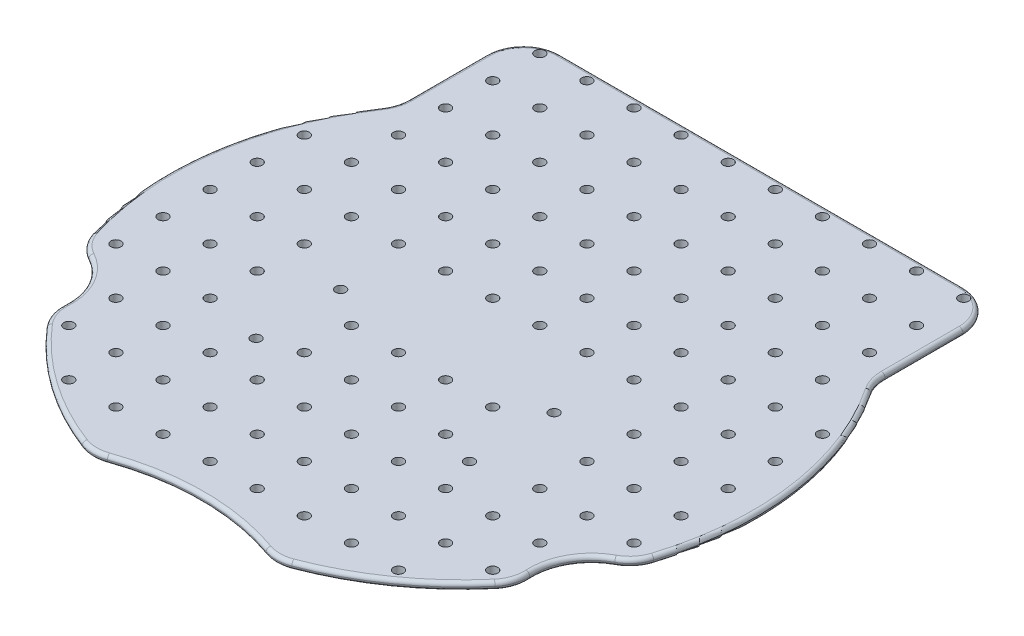
SolidWorks part; units mm, degrees
ref_plane "Front Plane" through (0, 0, 0) normal (0, 0, 1) x (1, 0, 0)
ref_plane "Top Plane" through (0, 0, 0) normal (0, 1, 0) x (1, 0, 0)
ref_plane "Right Plane" through (0, 0, 0) normal (1, 0, 0) x (0, 0, -1)
sketch "Sketch2" plane through (0, 0, 0) normal (0, 1, 0) x (1, 0, 0)
  line L0 (0, 0) -> (0, 108.8103) construction
  line L1 (0, 0) -> (176.5905, 0) construction
sketch "Top_lay" plane through (0, 0, 0) normal (0, 1, 0) x (1, 0, 0)
  line L0 (0, 0) -> (0, 108.8103) construction
  line L1 (-24.7551, -76.0736) -> (24.7551, -76.0736)
  arc A0 (24.7551, -76.0736) -> (-24.7551, -76.0736) centre (0, 0) ccw
  point P3 (0, -76.0223)
  dimension "D1" = 160
extrude "Boss-Extrude2" add sketch "Top_lay" along normal mid plane 2
sketch "Motor_Spacing" plane through (0, 1, 0) normal (0, 1, 0) x (1, 0, 0)
  line L0 (0, 0) -> (0, 108.8103) construction
  line L2 (64.7199, 81.3288) -> (-64.7199, 81.3288)
  line L3 (64.7199, 81.3288) -> (64.7199, 46.3288)
  line L4 (64.7199, 46.3288) -> (-64.7199, 46.3288)
  line L5 (-64.7199, 81.3288) -> (-64.7199, 46.3288)
  line L6 (64.7199, 81.3288) -> (-64.7199, 46.3288) construction
  line L7 (64.7199, 46.3288) -> (-64.7199, 81.3288) construction
  point P2 (0, 63.8288)
  dimension "D1" = 35
extrude "Boss-Extrude6" add sketch "Motor_Spacing" against normal blind 2
sketch "Clamps" plane through (0, 1, 0) normal (0, 1, 0) x (1, 0, 0)
  line L5 (0, 0) -> (0, 108.9952) construction
  line L11 (-64.7199, 81.3288) -> (-71.8617, 81.3288)
  line L12 (-64.7199, 81.3288) -> (-64.7199, 46.8057)
  line L13 (-64.7199, 46.8057) -> (-71.8617, 46.8057)
  line L14 (-71.8617, 81.3288) -> (-71.8617, 46.8057)
  line L15 (64.7199, 46.8057) -> (71.8617, 46.8057)
  line L16 (64.7199, 81.3288) -> (64.7199, 46.8057)
  line L17 (64.7199, 81.3288) -> (71.8617, 81.3288)
  line L18 (71.8617, 81.3288) -> (71.8617, 46.8057)
sketch "RPi_L298N_hatch" plane through (0, -1, 0) normal (0, -1, 0) x (1, 0, 0)
  line L0 (0, 0) -> (0, -108.8103) construction
  line L1 (-32.5, 0.5353) -> (32.5, 0.5353)
  line L2 (-32.5, 0.5353) -> (-32.5, 30.5353)
  line L3 (-32.5, 30.5353) -> (32.5, 30.5353)
  line L4 (32.5, 0.5353) -> (32.5, 30.5353)
  line L5 (-32.5, 0.5353) -> (32.5, 30.5353) construction
  line L6 (-32.5, 30.5353) -> (32.5, 0.5353) construction
  line L8 (-22, -11.6596) -> (22, -11.6596)
  line L9 (-22, -11.6596) -> (-22, -55.6596)
  line L10 (-22, -55.6596) -> (22, -55.6596)
  line L11 (22, -11.6596) -> (22, -55.6596)
  line L12 (-22, -11.6596) -> (22, -55.6596) construction
  line L13 (-22, -55.6596) -> (22, -11.6596) construction
  point P0 (0, 15.5353)
  point P7 (0, -33.6596)
  point P12 (0, -89.9264)
  dimension "D1" = 65
  dimension "D2" = 30
  dimension "D3" = 44
  dimension "D4" = 44
sketch "PIR_ULTRA" plane through (0, -1, 0) normal (0, -1, 0) x (1, 0, 0)
  line L0 (0, 0) -> (0, -108.8103) construction
  line L12 (22.5, 64.0502) -> (-22.5, 64.0502)
  line L13 (22.5, 64.0502) -> (22.5, 59.0502)
  line L18 (22.5, 59.0502) -> (-22.5, 59.0502)
  line L19 (-22.5, 64.0502) -> (-22.5, 59.0502)
  line L20 (22.5, 64.0502) -> (-22.5, 59.0502) construction
  line L21 (22.5, 59.0502) -> (-22.5, 64.0502) construction
  point P7 (0, 61.5502)
  dimension "D1" = 5
  dimension "D2" = 45
sketch "Sketch4" plane through (0, 1, 0) normal (0, 1, 0) x (1, 0, 0)
  line L0 (30.9083, 77.9119) -> (33.3167, 77.8645) construction
  line L5 (-70.5204, 79.9042) -> (-69.9756, 79.8935) construction
  line L6 (-70.5204, 77.1986) -> (-69.9756, 77.2093) construction
  line L7 (30.9083, 79.1909) -> (33.3167, 79.2382) construction
  line L8 (-31.8745, -49.4486) -> (-31.8745, -62.2486) construction
  line L9 (-58.2826, 77.4389) -> (-56.6233, 77.4715) construction
  line L10 (-58.2826, 79.6638) -> (-56.6233, 79.6312) construction
  line L11 (-45.7424, 79.4175) -> (-43.5734, 79.3749) construction
  line L12 (-45.7424, 77.6853) -> (-43.5734, 77.7279) construction
  line L13 (-33.1029, 77.9335) -> (-30.6228, 77.9823) construction
  line L14 (-33.1029, 79.1692) -> (-30.6228, 79.1205) construction
  line L15 (-20.3992, 78.9197) -> (-17.7363, 78.8674) construction
  line L16 (-20.3992, 78.1831) -> (-17.7363, 78.2354) construction
  line L17 (-7.6444, 78.6691) -> (-4.901, 78.6152) construction
  line L18 (-7.6444, 78.4336) -> (-4.901, 78.4875) construction
  line L19 (5.157, 78.6851) -> (7.8877, 78.7387) construction
  line L20 (5.157, 78.4177) -> (7.8877, 78.364) construction
  line L21 (18.0058, 78.1653) -> (20.629, 78.1138) construction
  line L22 (18.0058, 78.9375) -> (20.629, 78.989) construction
  line L23 (56.9741, 77.3998) -> (58.4311, 77.3712) construction
  line L24 (56.9741, 79.7029) -> (58.4311, 79.7315) construction
  line L25 (43.8811, 79.4457) -> (45.934, 79.4861) construction
  line L26 (43.8811, 77.657) -> (45.934, 77.6167) construction
  line L27 (-31.8745, -62.2486) -> (-31.8745, -55.8486) construction
  line L28 (-31.8745, -55.8486) -> (41.6099, -55.8486) construction
  circle A1 centre (-70.2745, 78.5514) radius 1.375
  circle A2 centre (-57.4745, 78.5514) radius 1.375
  circle A3 centre (-44.6745, 78.5514) radius 1.375
  circle A4 centre (-31.8745, 78.5514) radius 1.375
  circle A5 centre (-19.0745, 78.5514) radius 1.375
  circle A6 centre (-6.2745, 78.5514) radius 1.375
  circle A7 centre (6.5255, 78.5514) radius 1.375
  circle A8 centre (19.3255, 78.5514) radius 1.375
  circle A9 centre (32.1255, 78.5514) radius 1.375
  circle A10 centre (44.9255, 78.5514) radius 1.375
  circle A11 centre (57.7255, 78.5514) radius 1.375
  circle A12 centre (70.5255, 78.5514) radius 1.375
  circle A13 centre (-57.4745, 65.7514) radius 1.375
  circle A14 centre (-44.6745, 65.7514) radius 1.375
  circle A15 centre (-31.8745, 65.7514) radius 1.375
  circle A16 centre (-19.0745, 65.7514) radius 1.375
  circle A17 centre (-6.2745, 65.7514) radius 1.375
  circle A18 centre (6.5255, 65.7514) radius 1.375
  circle A19 centre (19.3255, 65.7514) radius 1.375
  circle A20 centre (32.1255, 65.7514) radius 1.375
  circle A21 centre (44.9255, 65.7514) radius 1.375
  circle A22 centre (57.7255, 65.7514) radius 1.375
  circle A23 centre (70.5255, 65.7514) radius 1.375
  circle A24 centre (-57.4745, 52.9514) radius 1.375
  circle A25 centre (-44.6745, 52.9514) radius 1.375
  circle A26 centre (-31.8745, 52.9514) radius 1.375
  circle A27 centre (-19.0745, 52.9514) radius 1.375
  circle A28 centre (-6.2745, 52.9514) radius 1.375
  circle A29 centre (6.5255, 52.9514) radius 1.375
  circle A30 centre (19.3255, 52.9514) radius 1.375
  circle A31 centre (32.1255, 52.9514) radius 1.375
  circle A32 centre (44.9255, 52.9514) radius 1.375
  circle A33 centre (57.7255, 52.9514) radius 1.375
  circle A34 centre (70.5255, 52.9514) radius 1.375
  circle A35 centre (-57.4745, 40.1514) radius 1.375
  circle A36 centre (-44.6745, 40.1514) radius 1.375
  circle A37 centre (-31.8745, 40.1514) radius 1.375
  circle A38 centre (-19.0745, 40.1514) radius 1.375
  circle A39 centre (-6.2745, 40.1514) radius 1.375
  circle A40 centre (6.5255, 40.1514) radius 1.375
  circle A41 centre (19.3255, 40.1514) radius 1.375
  circle A42 centre (32.1255, 40.1514) radius 1.375
  circle A43 centre (44.9255, 40.1514) radius 1.375
  circle A44 centre (57.7255, 40.1514) radius 1.375
  circle A46 centre (-57.4745, 27.3514) radius 1.375
  circle A47 centre (-44.6745, 27.3514) radius 1.375
  circle A48 centre (-31.8745, 27.3514) radius 1.375
  circle A49 centre (-19.0745, 27.3514) radius 1.375
  circle A50 centre (-6.2745, 27.3514) radius 1.375
  circle A51 centre (6.5255, 27.3514) radius 1.375
  circle A52 centre (19.3255, 27.3514) radius 1.375
  circle A53 centre (32.1255, 27.3514) radius 1.375
  circle A54 centre (44.9255, 27.3514) radius 1.375
  circle A55 centre (57.7255, 27.3514) radius 1.375
  circle A56 centre (70.5255, 27.3514) radius 1.375
  circle A57 centre (-57.4745, 14.5514) radius 1.375
  circle A58 centre (-44.6745, 14.5514) radius 1.375
  circle A59 centre (-31.8745, 14.5514) radius 1.375
  circle A60 centre (-19.0745, 14.5514) radius 1.375
  circle A61 centre (-6.2745, 14.5514) radius 1.375
  circle A62 centre (6.5255, 14.5514) radius 1.375
  circle A63 centre (19.3255, 14.5514) radius 1.375
  circle A64 centre (32.1255, 14.5514) radius 1.375
  circle A65 centre (44.9255, 14.5514) radius 1.375
  circle A66 centre (57.7255, 14.5514) radius 1.375
  circle A67 centre (70.5255, 14.5514) radius 1.375
  circle A68 centre (-57.4745, 1.7514) radius 1.375
  circle A69 centre (-44.6745, 1.7514) radius 1.375
  circle A76 centre (44.9255, 1.7514) radius 1.375
  circle A77 centre (57.7255, 1.7514) radius 1.375
  circle A78 centre (70.5255, 1.7514) radius 1.375
  circle A79 centre (-57.4745, -11.0486) radius 1.375
  circle A80 centre (-44.6745, -11.0486) radius 1.375
  circle A82 centre (-19.0745, -11.0486) radius 1.375
  circle A83 centre (-6.2745, -11.0486) radius 1.375
  circle A84 centre (6.5255, -11.0486) radius 1.375
  circle A85 centre (19.3255, -11.0486) radius 1.375
  circle A87 centre (44.9255, -11.0486) radius 1.375
  circle A88 centre (57.7255, -11.0486) radius 1.375
  circle A89 centre (70.5255, -11.0486) radius 1.375
  circle A90 centre (-57.4745, -23.8486) radius 1.375
  circle A91 centre (-44.6745, -23.8486) radius 1.375
  circle A93 centre (-19.0745, -23.8486) radius 1.375
  circle A94 centre (-6.2745, -23.8486) radius 1.375
  circle A95 centre (6.5255, -23.8486) radius 1.375
  circle A96 centre (19.3255, -23.8486) radius 1.375
  circle A98 centre (44.9255, -23.8486) radius 1.375
  circle A99 centre (57.7255, -23.8486) radius 1.375
  circle A100 centre (70.5255, -23.8486) radius 1.375
  circle A101 centre (-57.4745, -36.6486) radius 1.375
  circle A102 centre (-44.6745, -36.6486) radius 1.375
  circle A103 centre (-31.8745, -36.6486) radius 1.375
  circle A104 centre (-19.0745, -36.6486) radius 1.375
  circle A105 centre (-6.2745, -36.6486) radius 1.375
  circle A106 centre (6.5255, -36.6486) radius 1.375
  circle A107 centre (19.3255, -36.6486) radius 1.375
  circle A108 centre (32.1255, -36.6486) radius 1.375
  circle A109 centre (44.9255, -36.6486) radius 1.375
  circle A110 centre (57.7255, -36.6486) radius 1.375
  circle A111 centre (70.5255, -36.6486) radius 1.375
  circle A112 centre (-57.4745, -49.4486) radius 1.375
  circle A113 centre (-44.6745, -49.4486) radius 1.375
  circle A114 centre (-31.8745, -49.4486) radius 1.375
  circle A115 centre (-19.0745, -49.4486) radius 1.375
  circle A116 centre (-6.2745, -49.4486) radius 1.375
  circle A117 centre (6.5255, -49.4486) radius 1.375
  circle A118 centre (19.3255, -49.4486) radius 1.375
  circle A119 centre (32.1255, -49.4486) radius 1.375
  circle A120 centre (44.9255, -49.4486) radius 1.375
  circle A121 centre (57.7255, -49.4486) radius 1.375
  circle A122 centre (70.5255, -49.4486) radius 1.375
  circle A123 centre (-57.4745, -62.2486) radius 1.375
  circle A124 centre (-44.6745, -62.2486) radius 1.375
  circle A125 centre (-31.8745, -62.2486) radius 1.375
  circle A130 centre (32.1255, -62.2486) radius 1.375
  circle A131 centre (44.9255, -62.2486) radius 1.375
  circle A132 centre (57.7255, -62.2486) radius 1.375
  circle A133 centre (70.5255, -62.2486) radius 1.375
  circle A134 centre (-57.4745, -75.0486) radius 1.375
  circle A135 centre (-44.6745, -75.0486) radius 1.375
  circle A142 centre (44.9255, -75.0486) radius 1.375
  circle A143 centre (57.7255, -75.0486) radius 1.375
  circle A144 centre (70.5255, -75.0486) radius 1.375
  circle A145 centre (-70.2745, 65.7514) radius 1.375
  circle A146 centre (-70.2745, 52.9514) radius 1.375
  circle A148 centre (-70.2745, 27.3514) radius 1.375
  circle A149 centre (-70.2745, 14.5514) radius 1.375
  circle A150 centre (-70.2745, 1.7514) radius 1.375
  circle A151 centre (-70.2745, -11.0486) radius 1.375
  circle A152 centre (-70.2745, -23.8486) radius 1.375
  circle A153 centre (-70.2745, -36.6486) radius 1.375
  circle A154 centre (-70.2745, -49.4486) radius 1.375
  circle A155 centre (-70.2745, -62.2486) radius 1.375
  circle A156 centre (-70.2745, -75.0486) radius 1.375
  circle A157 centre (-6.2745, -62.2486) radius 1.375 [skipped]
  circle A158 centre (6.5255, -62.2486) radius 1.375 [skipped]
  circle A159 centre (-19.0745, -62.2486) radius 1.375 [skipped]
  circle A160 centre (19.3255, -62.2486) radius 1.375 [skipped]
  circle A161 centre (-31.8745, -23.8486) radius 1.375 [skipped]
  circle A162 centre (-31.8745, -11.0486) radius 1.375 [skipped]
  circle A163 centre (-31.8745, 1.7514) radius 1.375 [skipped]
  circle A164 centre (-19.0745, 1.7514) radius 1.375 [skipped]
  circle A165 centre (-6.2745, 1.7514) radius 1.375 [skipped]
  circle A166 centre (6.5255, 1.7514) radius 1.375 [skipped]
  circle A167 centre (19.3255, 1.7514) radius 1.375 [skipped]
  circle A168 centre (32.1255, 1.7514) radius 1.375 [skipped]
  circle A169 centre (32.1255, -11.0486) radius 1.375 [skipped]
  circle A170 centre (32.1255, -23.8486) radius 1.375 [skipped]
  circle A171 centre (19.3255, -75.0486) radius 1.375 [skipped]
  circle A172 centre (6.5255, -75.0486) radius 1.375 [skipped]
  circle A173 centre (-6.2745, -75.0486) radius 1.375 [skipped]
  circle A174 centre (-19.0745, -75.0486) radius 1.375 [skipped]
  circle A175 centre (-31.8745, -75.0486) radius 1.375 [skipped]
  circle A176 centre (32.1255, -75.0486) radius 1.375 [skipped]
  circle A177 centre (19.3255, -62.2486) radius 1.375
  circle A178 centre (6.5255, -62.2486) radius 1.375
  circle A179 centre (-6.2745, -62.2486) radius 1.375
  circle A180 centre (-19.0745, -62.2486) radius 1.375
  circle A181 centre (-70.2745, 40.1514) radius 1.375 [skipped]
  circle A182 centre (70.5255, 40.1514) radius 1.375 [skipped]
  point P0 (-1.6495, 78.5514)
  dimension "D1" = 38.4
  dimension "D4" = 12
  dimension "D5" = 13
extrude "Cut-Extrude5" cut sketch "Sketch4" against normal blind 10
sketch "Sketch5" plane through (0, -1, 0) normal (0, -1, 0) x (1, 0, 0)
  line L0 (0, 15.5353) -> (50.4781, 15.5353) construction
  line L1 (50.4781, 15.5353) -> (0, 15.5353) construction
  line L2 (0, 15.5353) -> (0, -13.6339) construction
  line L3 (-32.5, 30.5353) -> (32.5, 30.5353) construction
  line L4 (-32.5, 0.5353) -> (-32.5, 30.5353) construction
  circle A0 centre (-29, 27.0353) radius 1.375
  circle A1 centre (29, 27.0353) radius 1.375
  circle A2 centre (29, 4.0353) radius 1.375
  circle A3 centre (-29, 4.0353) radius 1.375
  dimension "D1" = 2.75
  dimension "D2" = 3.5
  dimension "D3" = 3.5
extrude "Cut-Extrude6" cut sketch "Sketch5" against normal blind 10
sketch "Sketch6" plane through (0, -1, 0) normal (0, -1, 0) x (1, 0, 0)
  line L0 (0, 0) -> (0, -9.0315) construction
  line L1 (0, 0) -> (0, -108.8103) construction
  line L2 (-24.7551, 76.0736) -> (24.7551, 76.0736)
  arc A0 (-74.6843, 28.675) -> (-63.7957, 48.2712) centre (-79.0381, 43.9174) ccw
  arc A1 (-71.4634, 35.958) -> (-64.7199, -47.0248) centre (0, 0) ccw construction
  arc A2 (-24.7551, 76.0736) -> (-70.3887, 38.0189) centre (0, 0) ccw construction
  arc A3 (-24.7551, 76.0736) -> (24.7551, 76.0736) centre (0, 135.9806) ccw
  arc A5 (-74.6843, 28.675) -> (-63.7957, 48.2712) centre (0, 0) cw
  arc A9 (74.6843, 28.675) -> (63.7957, 48.2712) centre (0, 0) ccw
  arc A10 (74.6843, 28.675) -> (63.7957, 48.2712) centre (79.0381, 43.9174) cw
extrude "Cut-Extrude9" cut sketch "Sketch6" against normal blind 10
fillet "Fillet1" radius 10 10 edges at (-64.7199, 0, -47.0248) (-64.7199, 0, -81.3288) (64.7199, 0, -81.3288) (64.7199, 0, -47.0248) (74.6843, 0, 28.675) (63.7957, 0, 48.2712) (24.7551, 0, 76.0736) (-24.7551, 0, 76.0736) (-63.7957, 0, 48.2712) (-74.6843, 0, 28.675)
fillet "Fillet2" radius 1 40 edges at (-62.713, 1, 48.6369) (-65.1815, 1, 36.218) (-74.423, 1, 27.5625) (-79.1963, 1, -11.3113) (-65.1538, 1, -47.2555) (-64.7199, 1, -60.7489) (-61.791, 1, -78.3998) (0, 1, -81.3288) (61.791, 1, -78.3998) (64.7199, 1, -60.7489) (65.1538, 1, -47.2555) (79.1963, 1, -11.3113) (74.423, 1, 27.5625) (65.1815, 1, 36.218) (62.713, 1, 48.6369) (46.0789, 1, 65.3968) (25.0171, 1, 75.4227) (0, 1, 71.1603) (-25.0171, 1, 75.4227) (-62.713, -1, 48.6369) (-65.1815, -1, 36.218) (-74.423, -1, 27.5625) (-79.1963, -1, -11.3113) (-65.1538, -1, -47.2555) (-64.7199, -1, -60.7489) (-61.791, -1, -78.3998) (0, -1, -81.3288) (61.791, -1, -78.3998) (64.7199, -1, -60.7489) (65.1538, -1, -47.2555) (79.1963, -1, -11.3113) (74.423, -1, 27.5625) (65.1815, -1, 36.218) (62.713, -1, 48.6369) (46.0789, -1, 65.3968) (25.0171, -1, 75.4227) (0, -1, 71.1603) (-25.0171, -1, 75.4227) (-46.0789, 1, 65.3968) (-46.0789, -1, 65.3968)
